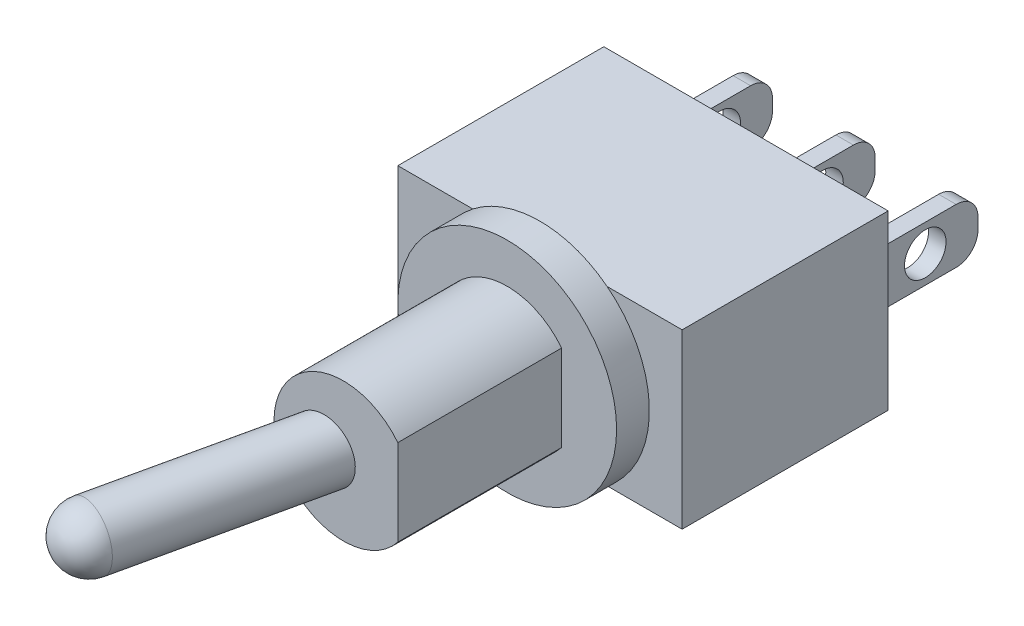
SolidWorks part; units mm, degrees
material "Nylon 101"
ref_plane "X-Y Datum" through (0, 0, 0) normal (0, 0, 1) x (1, 0, 0)
ref_plane "X-Z Datum" through (0, 0, 0) normal (0, 1, 0) x (1, 0, 0)
ref_plane "Y-Z Datum" through (0, 0, 0) normal (1, 0, 0) x (0, 0, -1)
sketch "Sketch2" plane through (0, 0, 0) normal (0, 0, 1) x (1, 0, 0)
  line L1 (6.5024, -3.9497) -> (-6.5024, -3.9497)
  line L2 (6.5024, -3.9497) -> (6.5024, 3.9497)
  line L3 (6.5024, 3.9497) -> (-6.5024, 3.9497)
  line L4 (-6.5024, -3.9497) -> (-6.5024, 3.9497)
  line L5 (6.5024, -3.9497) -> (-6.5024, 3.9497) construction
  line L6 (6.5024, 3.9497) -> (-6.5024, -3.9497) construction
  point P0 (0, 0)
  dimension "D1" = 13.0048
  dimension "D2" = 7.8994
extrude "Boss-Extrude1" add sketch "Sketch2" against normal blind 9.4234 contours L1 L4 L3 L2
sketch "Sketch5" plane through (0, 0, 0) normal (1, 0, 0) x (0, 0, -1)
  line L5 (9.4234, -3.9497) -> (9.4234, 3.9497) construction
  line L6 (9.4234, -1.25) -> (13.9352, -1.25)
  line L7 (9.4234, -1.25) -> (9.4234, 1.25)
  line L8 (9.4234, 1.25) -> (13.9352, 1.25)
  line L9 (14.9352, -0.25) -> (14.9352, 0.25)
  circle A1 centre (12.5234, 0) radius 0.95
  arc A2 (13.9352, -1.25) -> (14.9352, -0.25) centre (13.9352, -0.25) ccw
  arc A3 (13.9352, 1.25) -> (14.9352, 0.25) centre (13.9352, 0.25) cw
  point P6 (9.4234, 0)
  point P14 (14.9352, -1.25)
  point P17 (14.9352, 1.25)
  dimension "D2" = 1.9
  dimension "D5" = 1
  dimension "D1" = 2.5
  dimension "D3" = 5.5118
  dimension "D4" = 3.1
extrude "Boss-Extrude2" add sketch "Sketch5" along normal mid plane 0.8 from offset 4.7 contours A3 L8 L7 L6 A2 L9 A1 region at (0, 0, -9.4839)
pattern_linear "LPattern1" count 3 spacing 4.7 along (-1, 0, 0) of "Boss-Extrude2"
sketch "Sketch6" plane through (0, 0, 0) normal (0, 0, 1) x (1, 0, 0)
  circle A0 centre (0, 0) radius 5.0038
  dimension "D1" = 10.0076
extrude "Boss-Extrude3" add sketch "Sketch6" along normal blind 1.4986
sketch "Sketch7" plane through (0, 0, 1.4986) normal (0, 0, 1) x (1, 0, 0)
  line L0 (2.4892, -1.9709) -> (2.4892, 1.9709)
  line L1 (0, 0) -> (3.175, 0) construction
  arc A0 (2.4892, 1.9709) -> (2.4892, -1.9709) centre (0, 0) ccw
  dimension "D1" = 6.35
  dimension "D2" = 0.6858
  dimension "D3" = 3.175
extrude "Boss-Extrude5" add sketch "Sketch7" along normal blind 7.493
sketch "Sketch8" plane through (0, 0, 0) normal (0, 1, 0) x (1, 0, 0)
  line L0 (0, -1000) -> (0, 49000) construction
  line L1 (-3.1384, -19.1479) -> (0, -4.9916)
  line L2 (3.1384, -19.1479) -> (0, -4.9916) construction
  line L4 (-3.175, -8.9916) -> (2.4892, -8.9916) construction
  line L6 (0, -4.9916) -> (-1.3639, -4.6892)
  line L7 (-1.3639, -4.6892) -> (-4.1999, -17.4816)
  arc A0 (3.1384, -19.1479) -> (-3.1384, -19.1479) centre (0, -4.9916) cw construction
  arc A1 (-4.1999, -17.4816) -> (-3.1384, -19.1479) centre (-2.836, -17.784) ccw
  point P7 (0, -4.9916)
  point P8 (0, -19.4916)
  point P15 (0, -19.4916)
  dimension "D1" = 25
  dimension "D2" = 10.5
  dimension "D3" = 4
  dimension "D4" = 1.397
  dimension "D5" = 1.397
revolve "Revolve1" add sketch "Sketch8" angle 360 about L1
